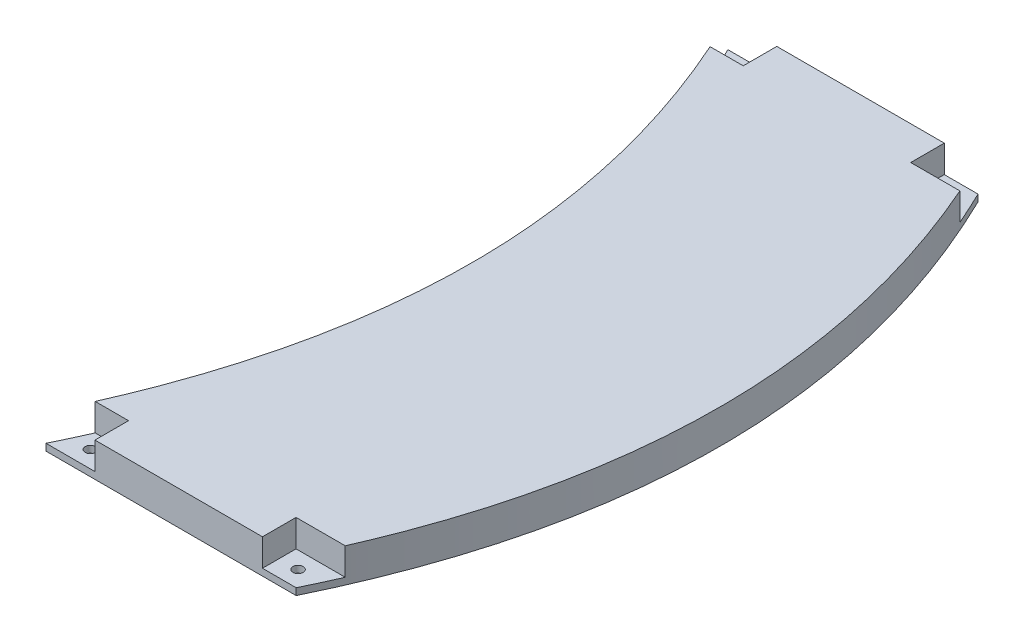
SolidWorks part; units mm, degrees
ref_plane "Alzado" through (0, 0, 0) normal (0, 0, 1) x (1, 0, 0)
ref_plane "Planta" through (0, 0, 0) normal (0, 1, 0) x (1, 0, 0)
ref_plane "Vista lateral" through (0, 0, 0) normal (1, 0, 0) x (0, 0, -1)
sketch "Croquis1" plane through (0, 0, 0) normal (0, 1, 0) x (1, 0, 0)
  line L1 (-100, 100) -> (100, 100)
  line L2 (-100, 100) -> (-100, -100)
  line L3 (-100, -100) -> (100, -100)
  line L4 (100, 100) -> (100, -100)
  line L5 (-100, 100) -> (100, -100) construction
  line L6 (-100, -100) -> (100, 100) construction
  point P0 (0, 0)
  dimension "D1" = 200
  dimension "D2" = 200
extrude "Saliente-Extruir1" add sketch "Croquis1" along normal blind 10
sketch "Croquis3" plane through (0, 10, 0) normal (0, 1, 0) x (1, 0, 0)
  line L0 (-356.0969, 70.707) -> (443.9031, 70.707) construction
  line L1 (-54.6589, 100) -> (18.7194, 100)
  line L2 (100, 100) -> (-100, 100) construction
  line L4 (-100, -100) -> (100, -100) construction
  line L6 (-54.6589, -100) -> (18.7194, -100)
  line L8 (100, 100) -> (-100, 100)
  line L9 (100, 100) -> (100, -100)
  line L10 (100, -100) -> (-100, -100)
  line L11 (-100, 100) -> (-100, -100)
  line L12 (100, 100) -> (-100, -100) construction
  line L13 (100, -100) -> (-100, 100) construction
  spline S0 degree 2 poles (-54.6589, 100) (-5.4377, 0.7428) (-54.6589, -100) knots 0 0 0 1 1 1
  spline S1 degree 2 poles (18.7194, 100) (67.2186, 0) (18.7194, -100) knots 0 0 0 1 1 1
  point P12 (0, 0)
  line M10 (100, -100) -> (100, 100)
  line M11 (100, 100) -> (-100, 100)
  line M12 (-100, 100) -> (-100, -100)
  line M13 (-100, -100) -> (100, -100)
extrude "Cortar-Extruir2" cut sketch "Croquis3" against normal blind 10 contours S0 M11 M12 M13 | S1 M11 M13 M10 region at (-68.69, 10, -0.0395) region at (67.0415, 10, 0)
sketch "Croquis4" plane through (0, 10, 0) normal (0, 1, 0) x (1, 0, 0)
  line L0 (0, 0) -> (-13.6187, 0) construction
  line L1 (-50.2966, -90.149) -> (-40.2966, -90.149)
  line L3 (-50.2966, -100.149) -> (-40.2966, -100.149)
  line L4 (-40.2966, -90.149) -> (-40.2966, -100.149)
  line L5 (-50.2966, -90.149) -> (-40.2966, -100.149) construction
  line L6 (-50.2966, -100.149) -> (-40.2966, -90.149) construction
  line L12 (8.8361, -90.149) -> (18.8361, -90.149)
  line L13 (8.8361, -90.149) -> (8.8361, -100.149)
  line L14 (8.8361, -100.149) -> (18.8361, -100.149)
  line L16 (8.8361, -90.149) -> (18.8361, -100.149) construction
  line L17 (8.8361, -100.149) -> (18.8361, -90.149) construction
  line L21 (-50.2966, -100.149) -> (-58.1203, -100.149)
  line L22 (-58.1203, -100.149) -> (-50.2966, -90.149)
  line L23 (18.8361, -90.149) -> (23.704, -90.149)
  line L24 (23.704, -90.149) -> (18.8361, -100.149)
  line L25 (8.8361, 90.149) -> (8.8361, 100.149)
  line L26 (8.8361, 100.149) -> (18.8361, 100.149)
  line L27 (23.704, 90.149) -> (18.8361, 100.149)
  line L28 (18.8361, 90.149) -> (23.704, 90.149)
  line L29 (8.8361, 90.149) -> (18.8361, 90.149)
  line L30 (-58.1203, 100.149) -> (-50.2966, 90.149)
  line L31 (-50.2966, 100.149) -> (-58.1203, 100.149)
  line L32 (-50.2966, 100.149) -> (-40.2966, 100.149)
  line L33 (-40.2966, 90.149) -> (-40.2966, 100.149)
  line L34 (-50.2966, 90.149) -> (-40.2966, 90.149)
  point P0 (-45.2966, -95.149)
  point P12 (13.8361, -95.149)
  point P22 (13.8361, 95.149)
  dimension "D1" = 10
  dimension "D2" = 10
  dimension "D3" = 10
  dimension "D4" = 10
extrude "Cortar-Extruir3" cut sketch "Croquis4" against normal blind 8
sketch "Croquis6" plane through (0, 2, 0) normal (0, 1, 0) x (1, 0, 0)
  line L0 (0, 0) -> (72.8864, 0) construction
  circle A0 centre (-46.58, -95.0745) radius 1.5
  circle A1 centre (14.3586, -95.0745) radius 1.5
  circle A2 centre (14.3586, 95.0745) radius 1.5
  circle A3 centre (-46.58, 95.0745) radius 1.5
  dimension "D1" = 3
  dimension "D2" = 3
extrude "Cortar-Extruir4" cut sketch "Croquis6" against normal blind 32
shell "Vaciado1" thickness 2 removed face at (-46.58, 0, -93.5745)
